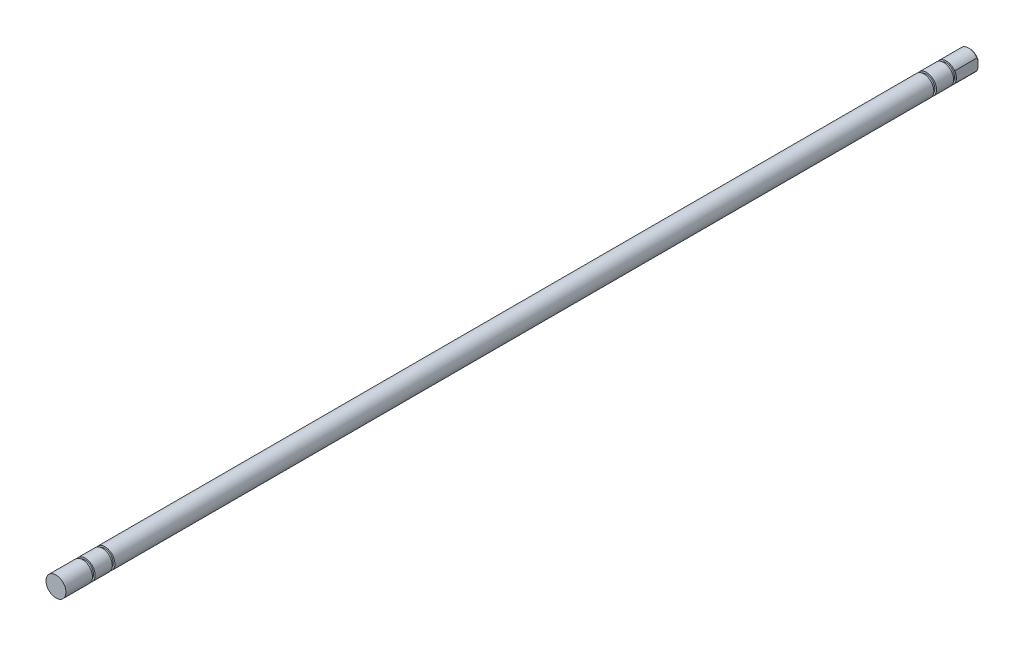
SolidWorks part; units mm, degrees
material "Titanium Ti-6Al-4V"
ref_plane "Front Plane" through (0, 0, 0) normal (0, 0, 1) x (1, 0, 0)
ref_plane "Top Plane" through (0, 0, 0) normal (0, 1, 0) x (1, 0, 0)
ref_plane "Right Plane" through (0, 0, 0) normal (1, 0, 0) x (0, 0, -1)
sketch "Sketch1" plane through (0, 0, 0) normal (0, 0, 1) x (1, 0, 0)
  circle A0 centre (0, 0) radius 3
extrude "Boss-Extrude1" add sketch "Sketch1" along normal blind 275
sketch "Sketch3" plane through (0, 0, 0) normal (1, 0, 0) x (0, 0, -1)
  line L0 (0, 3) -> (-275, 3) construction
  line L1 (-267, 3) -> (-266.2, 3)
  line L2 (-267, 3) -> (-267, 2.5)
  line L3 (-267, 2.5) -> (-266.2, 2.5)
  line L4 (-266.2, 3) -> (-266.2, 2.5)
  line L5 (-275, 3) -> (-275, -3) construction
  line L6 (-263.365, 0) -> (-260, 0) construction
  line L7 (-261.05, 3) -> (-260.25, 3)
  line L8 (-261.05, 3) -> (-261.05, 2.5)
  line L9 (-261.05, 2.5) -> (-260.25, 2.5)
  line L10 (-260.25, 3) -> (-260.25, 2.5)
  line L11 (-13.8, 3) -> (-13, 3)
  line L12 (-13.8, 3) -> (-13.8, 2.5)
  line L13 (-13.8, 2.5) -> (-13, 2.5)
  line L14 (-13, 3) -> (-13, 2.5)
  line L15 (-7.85, 3) -> (-7.05, 3)
  line L16 (-7.85, 3) -> (-7.85, 2.5)
  line L17 (-7.85, 2.5) -> (-7.05, 2.5)
  line L18 (-7.05, 3) -> (-7.05, 2.5)
  point P12 (-260.65, 2.5)
  point P21 (-7.05, 2.75)
  dimension "D1" = 0.8
  dimension "D2" = 0.5
  dimension "D3" = 8
  dimension "D4" = 0.5
  dimension "D5" = 0.8
  dimension "D6" = 13.95
  dimension "D7" = 5.15
  dimension "D8" = 0.5
  dimension "D9" = 0.8
  dimension "D10" = 0.5
  dimension "D11" = 0.8
  dimension "D12" = 5.15
  dimension "D13" = 261.2
revolve "Cut-Revolve1" cut sketch "Sketch3" angle 360 about L6
sketch "Sketch4" plane through (0, 0, 0) normal (0, 1, 0) x (1, 0, 0)
  line L0 (0, 6.9099) -> (0, -272.7358) construction
  line L1 (3, 0) -> (-3, 0) construction
  line L2 (2.5, 0) -> (5.9701, 0)
  line L3 (2.5, 0) -> (2.5, -7)
  line L4 (2.5, -7) -> (5.9701, -7)
  line L5 (5.9701, 0) -> (5.9701, -7)
  line L6 (-5.4253, 0) -> (-2.5, 0)
  line L7 (-5.4253, 0) -> (-5.4253, -7)
  line L8 (-5.4253, -7) -> (-2.5, -7)
  line L9 (-2.5, 0) -> (-2.5, -7)
  line L10 (3, -7.05) -> (3, 0) construction
  line L11 (-3, 0) -> (-3, -7.05) construction
  dimension "D1" = 7
  dimension "D2" = 0.5
  dimension "D3" = 0.5
extrude "Cut-Extrude2" cut sketch "Sketch4" against normal through all both and the other way through all
chamfer "Chamfer1" distance 0.3 angle 45 2 edges at (0, 3, 0) (0, -3, 0)
